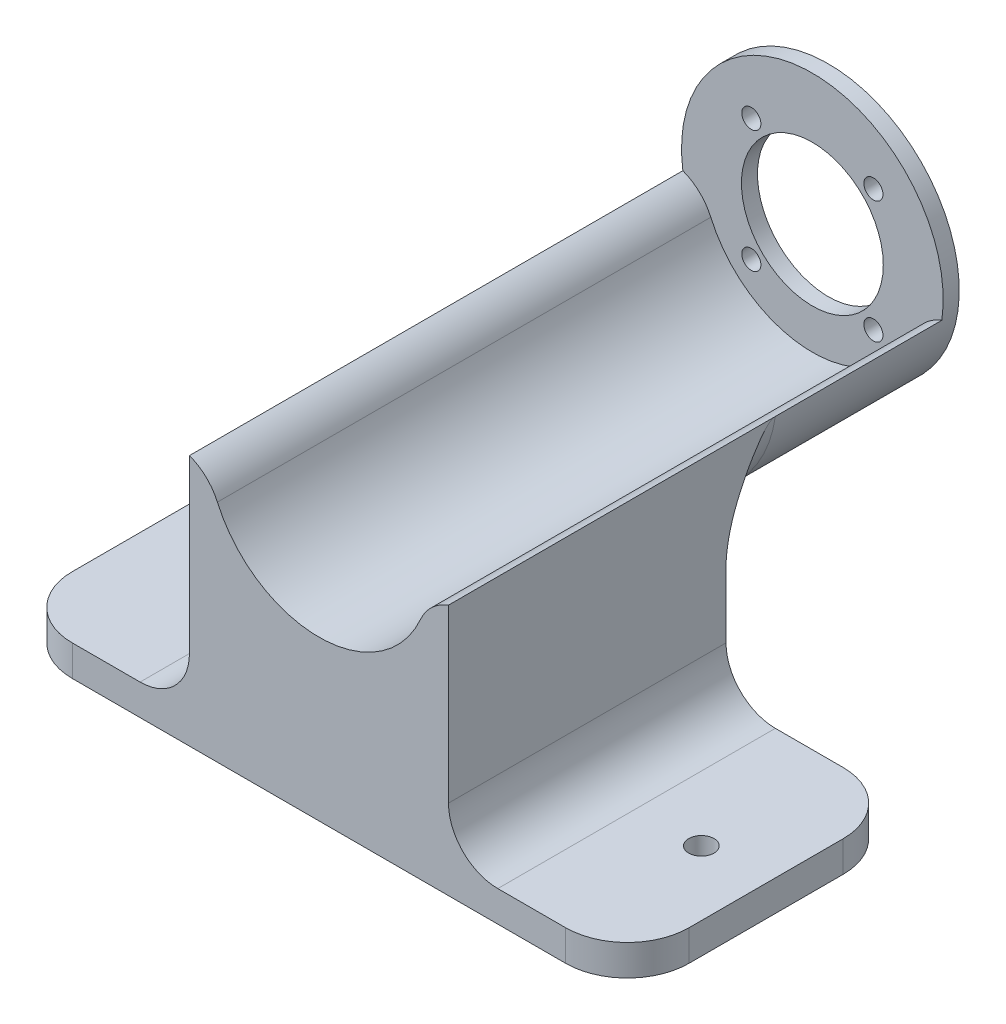
SolidWorks part; units mm, degrees
ref_plane "Alzado" through (0, 0, 0) normal (0, 0, 1) x (1, 0, 0)
ref_plane "Planta" through (0, 0, 0) normal (0, 1, 0) x (1, 0, 0)
ref_plane "Vista lateral" through (0, 0, 0) normal (1, 0, 0) x (0, 0, -1)
sketch "Croquis1" plane through (0, 0, 0) normal (0, 0, 1) x (1, 0, 0)
  line L1 (-50, -2.5) -> (50, -2.5)
  line L2 (-50, -2.5) -> (-50, 2.5)
  line L4 (50, -2.5) -> (50, 2.5)
  line L5 (-50, -2.5) -> (50, 2.5) construction
  line L6 (-50, 2.5) -> (50, -2.5) construction
  line L7 (-21, 38.3) -> (-21, 2.5)
  line L8 (21, 38.3) -> (21, 2.5)
  line L10 (-21, 38.3) -> (21, 2.5) construction
  line L11 (21, 38.3) -> (-21, 2.5) construction
  line L12 (0, -33.0776) -> (0, 118.0776) construction
  line L14 (-50, 2.5) -> (-21, 2.5)
  line L15 (21, 2.5) -> (50, 2.5)
  line L16 (21, 38.3) -> (17.7482, 38.3)
  line L17 (-17.7482, 38.3) -> (-21, 38.3)
  arc A1 (-17.7482, 38.3) -> (17.7482, 38.3) centre (0, 41.3) ccw
  point P0 (0, 0)
  point P7 (0, 20.4)
  dimension "D4" = 36
  dimension "D5" = 35.8
  dimension "D1" = 5
  dimension "D2" = 100
  dimension "D3" = 42
  dimension "D6" = 29
  dimension "D7" = 3
extrude "Saliente-Extruir1" add sketch "Croquis1" along normal blind 45
sketch "Croquis2" plane through (0, 2.5, 0) normal (0, 1, 0) x (1, 0, 0)
  line L0 (0, -69.5294) -> (0, 16.091) construction
  line L1 (-50, -45) -> (-50, 0) construction
  line L3 (-21, -45) -> (-50, -45) construction
  circle A0 centre (-39.5, -22.5) radius 2.05
  circle A1 centre (39.5, -22.5) radius 2.05
  dimension "D1" = 4.1
  dimension "D3" = 22.5
  dimension "D2" = 10.5
extrude "Cortar-Extruir1" cut sketch "Croquis2" against normal through all
fillet "Redondeo1" radius 10 4 edges at (50, 0, 0) (50, 0, 45) (-50, 0, 45) (-50, 0, 0)
fillet "Redondeo4" radius 8 2 edges at (21, 2.5, 22.5) (-21, 2.5, 22.5)
sketch "Croquis4" plane through (0, 0, 0) normal (0, 0, -1) x (-1, 0, 0)
  circle A4 centre (0, 41.3) radius 21.2132
  circle A5 centre (0, 41.3) radius 14 construction
  circle A6 centre (-9.9, 51.199) radius 1.55
  circle A7 centre (9.9, 51.199) radius 1.55
  circle A8 centre (9.9, 31.399) radius 1.55
  circle A9 centre (-9.9, 31.399) radius 1.55
  point P16 (0, 41.299)
  dimension "D1" = 28
  dimension "D2" = 3.1
  dimension "D4" = 9.9
  dimension "D5" = 19.8
  dimension "D3" = 4
extrude "Saliente-Extruir2" add sketch "Croquis4" along normal blind 37.6
sketch "Croquis5" plane through (0, 0, 45) normal (0, 0, 1) x (1, 0, 0)
  line L0 (17.7482, 38.3) -> (24.347, 38.3)
  line L1 (-24.347, 106.038) -> (24.347, 106.038)
  line L2 (-24.347, 106.038) -> (-24.347, 38.3)
  line L3 (-24.347, 38.3) -> (-17.7482, 38.3)
  line L4 (24.347, 106.038) -> (24.347, 38.3)
  line L5 (-24.347, 106.038) -> (24.347, 38.3) construction
  line L6 (-24.347, 38.3) -> (24.347, 106.038) construction
  arc A0 (-17.7482, 38.3) -> (17.7482, 38.3) centre (0, 41.3) ccw
  point P3 (0, 72.169)
extrude "Cortar-Extruir2" cut sketch "Croquis5" against normal blind 80
fillet "Redondeo6" radius 8 2 edges at (17.7482, 38.3, 5) (-17.7482, 38.3, 5)
fillet "Redondeo7" radius 8 1 edges at (0, 20.0868, 0)
sketch "Croquis6" plane through (0, 0, -35) normal (0, 0, 1) x (1, 0, 0)
  circle A0 centre (0, 41.3) radius 11.5
  dimension "D1" = 23
extrude "Cortar-Extruir3" cut sketch "Croquis6" against normal through all
